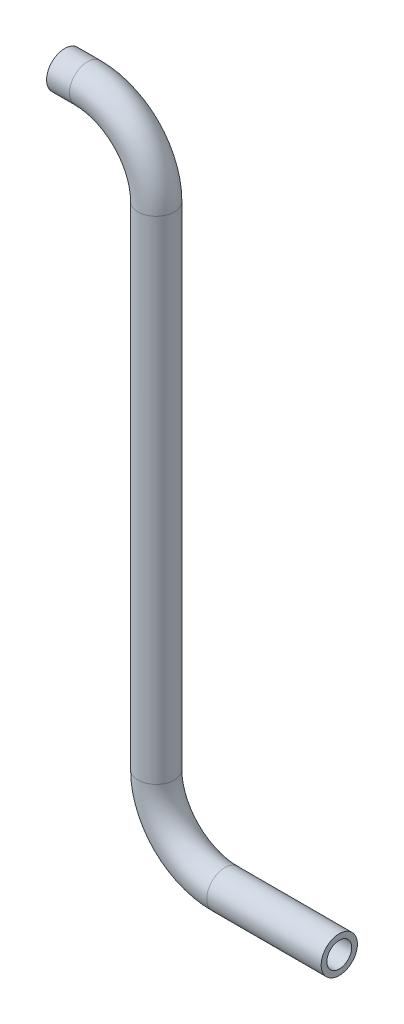
SolidWorks part; units mm, degrees
ref_plane "Piano frontale" through (0, 0, 0) normal (0, 0, 1) x (1, 0, 0)
ref_plane "Piano superiore" through (0, 0, 0) normal (0, 1, 0) x (1, 0, 0)
ref_plane "Piano destro" through (0, 0, 0) normal (1, 0, 0) x (0, 0, -1)
sketch "Schizzo1" plane through (0, 0, 0) normal (0, 0, 1) x (1, 0, 0)
  line L0 (0, 6) -> (0, 49)
  line L1 (-6, 55) -> (-8, 55)
  line L2 (6, 0) -> (16, 0)
  line L3 (-8, 59.2129) -> (-8, 78.6123) construction
  arc A0 (0, 49) -> (-6, 55) centre (-6, 49) ccw
  arc A1 (0, 6) -> (6, 0) centre (6, 6) ccw
  point P7 (0, 55)
  point P10 (0, 0)
  dimension "D3" = 6
  dimension "D1" = 55
  dimension "D2" = 10
  dimension "D4" = 90
  dimension "D5" = 90
sweep "Sweep-Sottile1" add path "Schizzo1" circular profile diameter 3.17 parameters "D1"=0.5, "D3"=3.17
